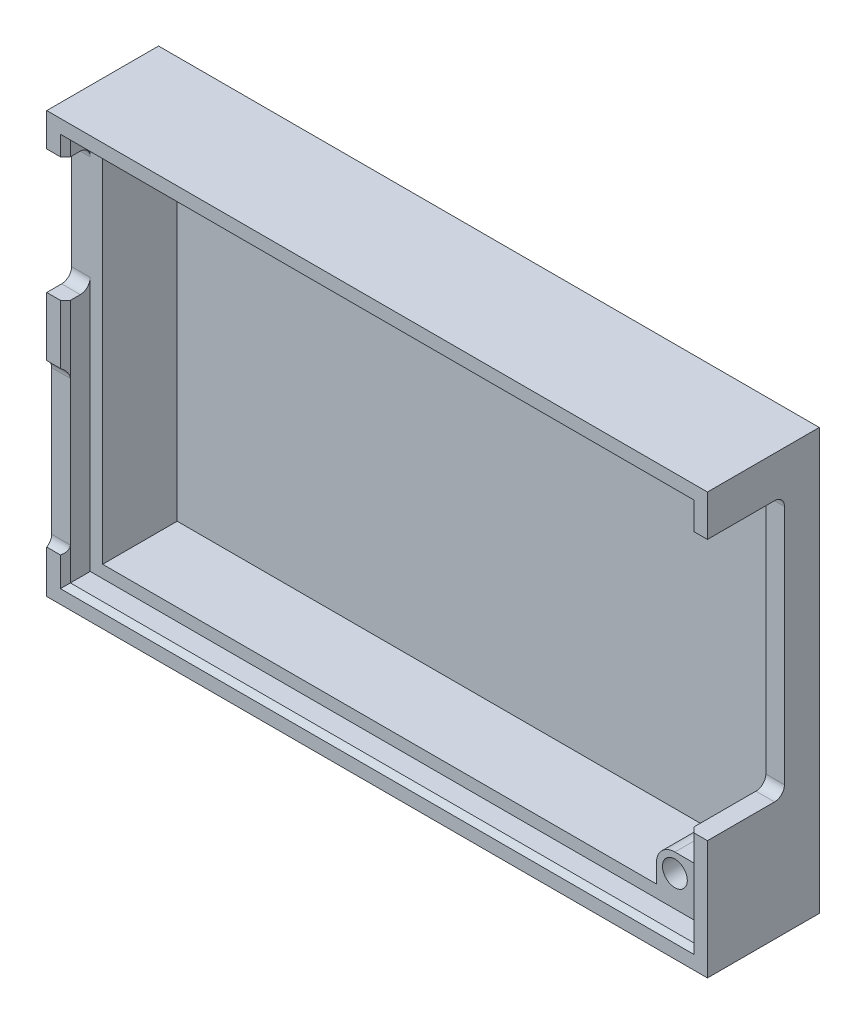
SolidWorks part; units mm, degrees
ref_plane "Спереди" through (0, 0, 0) normal (0, 0, 1) x (1, 0, 0)
ref_plane "Сверху" through (0, 0, 0) normal (0, 1, 0) x (1, 0, 0)
ref_plane "Справа" through (0, 0, 0) normal (1, 0, 0) x (0, 0, -1)
sketch "Эскиз1" plane through (0, 0, 0) normal (0, 0, 1) x (1, 0, 0)
  line L0 (48.984, 29.68) -> (49.984, 29.68)
  line L1 (0, 0) -> (49.784, 0) construction
  line L2 (0, 0) -> (0, 30.48) construction
  line L3 (0, 30.48) -> (49.784, 30.48) construction
  line L4 (49.784, 0) -> (49.784, 30.48) construction
  line L5 (-0.2, -0.2) -> (49.984, -0.2)
  line L6 (-0.2, -0.2) -> (-0.2, 30.68)
  line L7 (-0.2, 30.68) -> (49.984, 30.68)
  line L8 (49.984, -0.2) -> (49.984, 30.68)
  line L9 (0.8, 0.8) -> (48.984, 0.8)
  line L10 (0.8, 0.8) -> (0.8, 29.68)
  line L11 (0.8, 29.68) -> (48.984, 29.68)
  line L12 (48.984, 0.8) -> (48.984, 29.68)
  line L13 (48.984, 6) -> (49.984, 6)
  line L14 (46.863, 3.772) -> (48.984, 3.772)
  line L15 (-1.7, -1.7) -> (51.484, -1.7)
  line L16 (-1.7, -1.7) -> (-1.7, 32.18)
  line L17 (-1.7, 32.18) -> (51.484, 32.18)
  line L18 (51.484, -1.7) -> (51.484, 32.18)
  line L19 (45.377, 2.286) -> (45.377, 0.8)
  circle A0 centre (46.863, 2.286) radius 1
  circle A1 centre (46.863, 2.286) radius 1.486
  dimension "D18" = 2
  dimension "D1" = 30.48
  dimension "D2" = 49.784
  dimension "D3" = 0.8
  dimension "D4" = 0.8
  dimension "D5" = 0.8
  dimension "D6" = 0.8
  dimension "D7" = 6
  dimension "D8" = 0.2
  dimension "D9" = 0.2
  dimension "D10" = 0.2
  dimension "D11" = 0.2
  dimension "D12" = 1.5
  dimension "D13" = 1.5
  dimension "D14" = 1.5
  dimension "D15" = 1.5
  dimension "D16" = 46.863
  dimension "D17" = 2.286
extrude "Бобышка-Вытянуть1" add sketch "Эскиз1" along normal blind 1 contours L9 L12 L11 L10 | L12 L13 L8 L0 | A0 region at (24.7262, 15.3365, 0) region at (49.484, 17.84, 0)
extrude "Бобышка-Вытянуть2" add sketch "Эскиз1<3>" along normal blind 7 contours L13 L12 L9 L10 L11 L0 L8 L7 L6 L5 | A1 L9 L12 L14 | A1 L19 L9 | A1 A0 region at (24.892, 30.2692, 0) region at (48.4494, 2.286, 0) region at (45.7089, 1.1319, 0) region at (47.884, 3.307, 0)
sketch "Эскиз1<3>" plane through (0, 0, 0) normal (0, 0, 1) x (1, 0, 0) same geometry as "Эскиз1"
extrude "Бобышка-Вытянуть3" add sketch "Эскиз1<4>" along normal blind 9 contours L15 L18 L17 L16 L8 L5 L6 L7 region at (-1.0694, 15.24, 0)
sketch "Эскиз1<4>" plane through (0, 0, 0) normal (0, 0, 1) x (1, 0, 0) same geometry as "Эскиз1"
sketch "Эскиз2" plane through (49.984, 0, 0) normal (-1, 0, 0) x (0, 0, 1)
  line L0 (9, -0.2) -> (9, 30.68) construction
  line L1 (9, 7.874) -> (2.8, 7.874)
  line L2 (9, 7.874) -> (9, 28.874)
  line L3 (9, 28.874) -> (2.8, 28.874)
  line L4 (2.8, 7.874) -> (2.8, 28.874)
  line L5 (7, 6) -> (1, 6) construction
  point P8 (2.8, 18.374)
  dimension "D1" = 12.374
  dimension "D2" = 21
  dimension "D3" = 6.2
extrude "Вырез-Вытянуть1" cut sketch "Эскиз2" against normal through all
sketch "Эскиз3" plane through (-0.2, 0, 0) normal (1, 0, 0) x (0, 0, -1)
  line L0 (-9, -0.2) -> (-9, 30.68) construction
  line L1 (-9, 29.5) -> (-7, 29.5)
  line L2 (-9, 29.5) -> (-9, 19.5)
  line L3 (-9, 19.5) -> (-7, 19.5)
  line L4 (-7, 29.5) -> (-7, 19.5)
  line L5 (-7, -0.2) -> (-7, 30.68) construction
  line L6 (-9, -0.2) -> (-7, -0.2) construction
  point P10 (-9, 24.5)
  dimension "D1" = 24.7
  dimension "D2" = 10
extrude "Вырез-Вытянуть2" cut sketch "Эскиз3" against normal through all
sketch "Эскиз4" plane through (-0.2, 0, 0) normal (1, 0, 0) x (0, 0, -1)
  line L0 (-9, -0.2) -> (-9, 19.5) construction
  line L1 (-9, 14.75) -> (-8.6, 14.75)
  line L2 (-9, 14.75) -> (-9, 1.75)
  line L3 (-9, 1.75) -> (-8.6, 1.75)
  line L4 (-8.6, 14.75) -> (-8.6, 1.75)
  line L5 (-9, -0.2) -> (-7, -0.2) construction
  point P8 (-9, 8.25)
  dimension "D1" = 8.45
  dimension "D2" = 13
  dimension "D3" = 0.4
extrude "Вырез-Вытянуть3" cut sketch "Эскиз4" against normal through all
fillet "Скругление1" radius 0.8 6 edges at (50.734, 7.874, 2.8) (50.734, 28.874, 2.8) (-0.95, 19.5, 7) (-0.95, 29.5, 7) (-0.95, 1.75, 8.6) (-0.95, 14.75, 8.6)
chamfer "Фаска1" distance 0.4 angle 45 7 edges at (-0.2, 17.125, 9) (-0.2, 0.775, 9) (24.892, -0.2, 9) (49.984, 3.837, 9) (49.984, 29.777, 9) (24.892, 30.68, 9) (-0.2, 30.09, 9)
